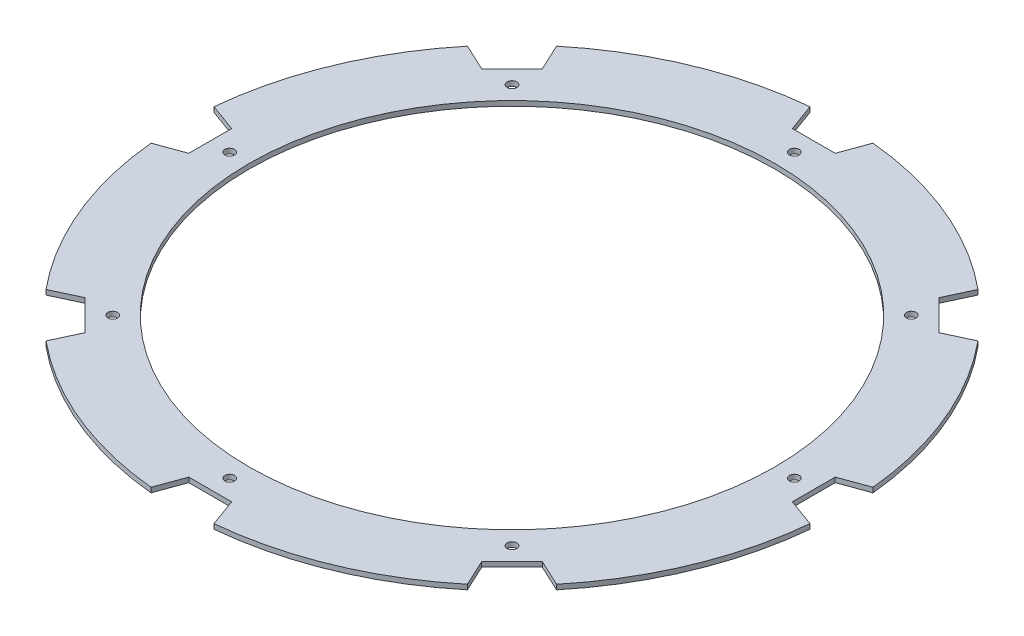
SolidWorks part; units mm, degrees
ref_plane "Front Plane" through (0, 0, 0) normal (0, 0, 1) x (1, 0, 0)
ref_plane "Top Plane" through (0, 0, 0) normal (0, 1, 0) x (1, 0, 0)
ref_plane "Right Plane" through (0, 0, 0) normal (1, 0, 0) x (0, 0, -1)
sketch "Sketch2" plane through (0, 0, 0) normal (0, 1, 0) x (1, 0, 0)
  line L0 (-215.9, 0) -> (-171.45, 0) construction
  line L1 (-171.45, 0) -> (0, 0) construction
  line L2 (0, 0) -> (171.45, 0) construction
  line L3 (171.45, 0) -> (215.9, 0) construction
  line L4 (-196.85, 13.97) -> (-196.85, -13.97)
  line L5 (-196.85, 13.97) -> (-214.9201, 20.547)
  line L6 (-196.85, -13.97) -> (-214.9201, -20.547)
  circle A0 centre (0, 0) radius 171.45
  circle A1 centre (0, 0) radius 215.9
  circle A2 centre (-184.15, 0) radius 3.175
  point P6 (-215.203, 17.3348)
  point P10 (-196.85, 0)
  point P12 (-196.85, 0)
  point P13 (-196.85, 0)
  point P15 (-171.45, 0)
  dimension "D1" = 342.9
  dimension "D2" = 431.8
  dimension "D7" = 6.35
  dimension "D3" = 27.94
  dimension "D4" = 40
  dimension "D6" = 25.4
  dimension "D8" = 12.7
extrude "Boss-Extrude1" add sketch "Sketch2" along normal blind 3.175 contours A1 A2 A0 region at (-203.7988, 0, -22.9903)
pattern_circular "CirPattern1" count 8 over 360 about axis through (0, 3.175, 0) along (0, -1, 0) reverse direction yes of face at (-184.15, 3.175, 3.175) of face at (-196.85, 1.5875, 0) of face at (-205.885, 1.5875, 17.2585) of face at (-205.885, 1.5875, -17.2585)
